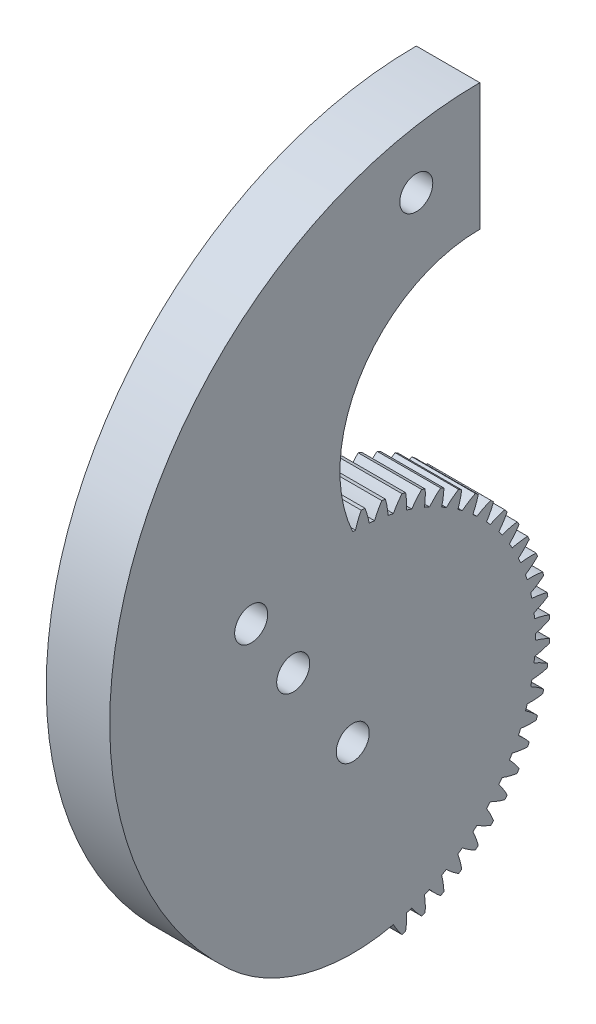
SolidWorks part; units mm, degrees
material "PLA"
ref_plane "Plane1" through (0, 0, 0) normal (0, 0, 1) x (1, 0, 0)
ref_plane "Plane2" through (0, 0, 0) normal (0, 1, 0) x (1, 0, 0)
ref_plane "Plane3" through (0, 0, 0) normal (1, 0, 0) x (0, 0, -1)
sketch "HoldingSke" plane through (0, 0, 0) normal (0, 1, 0) x (1, 0, 0)
  line L0 (0, 0) -> (0.866, -0.5)
  line L1 (-15, 0) -> (100, 0) construction
  line L2 (0, 0) -> (-2.1039, 2.3779)
  line L3 (0, 0) -> (-11.863, 4.5341)
  line L4 (0, 0) -> (7.479, 4.318)
  line L5 (0, 0) -> (-46.8476, -17.4728)
  line L6 (0, 0) -> (-4.9738, -3.3558)
  line L7 (-2.1039, 2.3779) -> (8.6586, 51.2059)
  line L8 (-76.2, 54.61) -> (-75.3, 54.61)
  line L9 (-71.009, 38.7566) -> (-53.1078, 45.2721)
  line L10 (-76.2, 71.12) -> (104.1128, 71.12)
  line L11 (0, 0) -> (-6, 0)
  line L12 (-76.2, 101.6) -> (-76.162, 101.6)
  line L13 (24.9733, 27.94) -> (52.9518, 28.4284)
  line L14 (24.9733, 27.94) -> (24.9743, 27.94)
  line L15 (24.9733, 27.94) -> (100.4006, 29.5858)
  line L16 (-63.627, -1) -> (-12.827, -1)
  circle A0 centre (0, 0) radius 2.5
  circle A1 centre (0, 0) radius 13.749
  circle A2 centre (0, 0) radius 37.5
  circle A3 centre (0, 0) radius 2.5
  dimension "Num_teeth" = 30
  dimension "Pitch_radius" = 180.3128
  dimension "Width" = 6
sketch "BasProSke" plane through (0, 0, 0) normal (0, 1, 0) x (1, 0, 0)
  line L0 (-10, 0) -> (60, 0) construction
  line L1 (0, 0) -> (0, 15.5255)
  line L2 (0, 0) -> (5, 0)
  line L3 (5, 0) -> (5, 15.5255)
  line L4 (5, 15.5255) -> (0, 15.5255)
  dimension "Thickness" = 5
  dimension "Diameter" = 31.051
revolve "Base-Revolve" add sketch "BasProSke" angle 360 about L0
sketch "TooCutSke" plane through (0, 0, 0) normal (1, 0, 0) x (0, 0, -1)
  line L1 (0, 0) -> (0, 107) construction
  line L2 (0, 0) -> (-0.4263, 14.9939) construction
  line L3 (0, 0) -> (-1.5696, 29.9503) construction
  line L4 (-0.4263, 14.9939) -> (-0.7848, 14.9752) construction
  arc A0 (0.2153, 14.3724) -> (-0.2153, 14.3724) centre (0, 0) ccw
  arc A1 (0.6632, 15.5113) -> (-0.6632, 15.5113) centre (0, 0) ccw
  circle A2 centre (0, 0) radius 15 construction
  circle A3 centre (0, 0) radius 14.0954 construction
  arc A4 (-0.2153, 14.3724) -> (-0.6632, 15.5113) centre (-5.9939, 12.7575) ccw
  arc A5 (0.6632, 15.5113) -> (0.2153, 14.3724) centre (5.9939, 12.7575) ccw
extrude "ToothCut" cut sketch "TooCutSke" along normal through all
fillet "Breaks" [suppressed] radius 0.02 tangent propagation no
fillet "RootFillets" [suppressed] radius 0.251
pattern_circular "TeethCuts" count 60 every 6 about axis through (-10, 0, 0) along (1, 0, 0) of "ToothCut"
sketch "HubNeaOneSke" plane through (0, 0, 0) normal (-1, 0, 0) x (0, 0, 1)
  circle A0 centre (0, 0) radius 13.749
  dimension "Diameter" = 27.498
extrude "HubNearOne" [suppressed] add sketch "HubNeaOneSke" along normal blind 45.0001
sketch "HubNeaBotSke" plane through (0, 0, 0) normal (-1, 0, 0) x (0, 0, 1)
  circle A0 centre (0, 0) radius 13.749
  dimension "Diameter" = 27.498
extrude "HubNearBoth" [suppressed] add sketch "HubNeaBotSke" along normal blind 22.5
ref_plane "FarPln" through (5, 0, 0) normal (1, 0, 0) x (0, 0, -1)
sketch "HubFarSke" plane through (5, 0, 0) normal (1, 0, 0) x (0, 0, -1)
  circle A0 centre (0, 0) radius 13.749
  dimension "Diameter" = 27.498
extrude "HubFar" [suppressed] add sketch "HubFarSke" along normal blind 22.5
sketch "BorSke" plane through (0, 0, 0) normal (1, 0, 0) x (0, 0, -1)
  circle A0 centre (0, 0) radius 1.3
  dimension "Diameter" = 2.6
extrude "Bore" cut sketch "BorSke" along normal mid plane 100.0001
sketch "KeySke" plane through (0, 0, 0) normal (1, 0, 0) x (0, 0, -1)
  line L0 (-1, 0) -> (-1, 3.4)
  line L1 (-1, 3.4) -> (1, 3.4)
  line L2 (1, 3.4) -> (1, 0)
  line L3 (0, 0) -> (0, 34) construction
  line L4 (-1, 0) -> (1, 0)
  dimension "Width" = 2
extrude "Keyway" [suppressed] cut sketch "KeySke" along normal mid plane 100.0001
pattern_circular "Keyway2" [suppressed] count 2 every 90 about axis through (-10, 0, 0) along (1, 0, 0) reverse direction yes
sketch "Szkic1" plane through (5, 0, 0) normal (1, 0, 0) x (0, 0, -1)
  line L0 (0, 14.374) -> (0, 20.6333)
  line L1 (2.9482, -14.0684) -> (4.2597, -19.1168)
  arc A0 (-0.731, 20.9085) -> (4.2597, -19.1168) centre (1.7643, 0.8958) ccw
  arc A1 (0, 14.374) -> (2.9482, -14.0684) centre (0, 0) ccw
  arc A2 (2.7776, -14.1031) -> (3.1988, -14.0135) centre (0, 0) ccw construction
  dimension "D1" = 14.374
extrude "Wytnij-wyciągnięcie1" cut sketch "Szkic1" against normal through all and the other way through all contours A0 L1 A1 L0
sketch "Szkic2" plane through (0, 0, 0) normal (1, 0, 0) x (0, 0, -1)
  line L1 (10, 30) -> (10, 40)
  circle A0 centre (0, 0) radius 15.5255 construction
  arc A1 (10, 30) -> (0, 14.374) centre (10, 18.9872) ccw
  arc A2 (0.2153, 14.3724) -> (3.1988, -14.0135) centre (0, 0) ccw construction
  arc A3 (10, 40) -> (-9.7357, -10.5748) centre (10, 10.8619) ccw
  arc A4 (-9.7357, -10.5748) -> (0, 14.374) centre (0, 0) cw
  arc A5 (0.9618, 15.4957) -> (0.6632, 15.5113) centre (0, 0) ccw construction
  dimension "D3" = 10
  dimension "D1" = 40
  dimension "D2" = 10
extrude "Dodanie-wyciągnięcie1" add sketch "Szkic2" along normal up to surface (5 mm away) up to face at (5, 0, 1.3)
hole_wizard "Otwór pod śrubę M21" positions "Szkic3" profile "Szkic4" hole size "M2" standard "ISO" end condition up to next
sketch "Szkic3" plane through (5, 0, 0) normal (1, 0, 0) x (0, 0, -1)
  line L0 (10, 40) -> (10, 30) construction
  point P0 (5, 35)
  dimension "D1" = 5
  dimension "D2" = 5
sketch "Szkic4" plane through (5, 35, -5) normal (0, 1, 0) x (0, 0, -1)
  line L0 (0, 0) -> (0, 5)
  line L1 (0, 5) -> (1.3, 5)
  line L2 (1.3, 5) -> (1.3, 0)
  line L5 (1.3, 0) -> (0, 0)
  line L11 (0, -6.35) -> (0, 107.95) construction
  dimension "Średnica otworu na wylot" = 2.6
  dimension "Głębokość otworu na wylot" = 5
hole_wizard "Otwór pod śrubę M22" positions "Szkic6" profile "Szkic7" hole size "M2" standard "ISO" end condition up to next
sketch "Szkic6" plane through (5, 0, 0) normal (1, 0, 0) x (0, 0, -1)
  line L0 (0, 0) -> (-8, 12.0934) construction
  circle A0 centre (0, 0) radius 1.3 construction
  circle A1 centre (0, 0) radius 1.3 construction
  point P0 (-8, 12.0934)
  point P9 (-4.6897, 7.0892)
  dimension "D1" = 14.5
  dimension "D2" = 8
  dimension "D3" = 6
sketch "Szkic7" plane through (5, 12.0934, 8) normal (0, 1, 0) x (0, 0, -1)
  line L0 (0, 0) -> (0, 5)
  line L1 (0, 5) -> (1.3, 5)
  line L2 (1.3, 5) -> (1.3, 0)
  line L5 (1.3, 0) -> (0, 0)
  line L11 (0, -6.35) -> (0, 107.95) construction
  dimension "Średnica otworu na wylot" = 2.6
  dimension "Głębokość otworu na wylot" = 5
sketch "Szkic8" plane through (0, 0, 0) normal (1, 0, 0) x (0, 0, -1)
  circle A0 centre (0, 0) radius 3.4
  dimension "D1" = 6.8
extrude "Wytnij-wyciągnięcie2" cut sketch "Szkic8" along normal blind 2
ref_plane "Blat stołu" through (5, 0, 0) normal (1, 0, 0) x (0, 0, -1)
equation "' \"Module@HoldingSke\" = 6.35"
equation "' \"Num_teeth@HoldingSke\" = 12"
equation "' \"Ap@HoldingSke\" =  20"
equation "' \"Ap@HoldingSke\" = 20"
equation "' \"Width@HoldingSke\" = 0.5 * 25.4"
equation "' \"Hub_dia@HoldingSke\"= 1 * 25.4"
equation "' \"Hub_dia@HoldingSke\" = 1 * 25.4"
equation "' \"Overall_len@HoldingSke\" = 1.0 * 25.4"
equation "' \"Bore@HoldingSke\" = 0.75 * 25.4"
equation "' \"T_dim@HoldingSke\" = 0.1 * 25.4"
equation "' \"Width@KeySke\" = 0.25 * 25.4"
equation "' \"Show_teeth@HoldingSke\" = 13"
equation "' \"Backlash@HoldingSke\" = 0.009 * 25.4"
equation "' \"Addendum_fac@HoldingSke\" = 1.0"
equation "' \"Dedendum_fac@HoldingSke\" = 1.25"
equation "' \"Dedendum_add@HoldingSke\" = 0.00005 * 25.4"
equation "' \"Clearance_fac@HoldingSke\" = 0.25"
equation "\"Pitch@HoldingSke\" = 1 / \"Module@HoldingSke\""
equation "\"Pitch_dia@TooCutSke\" = \"Num_teeth@HoldingSke\" / \"Pitch@HoldingSke\""
equation "\"Base_dia@TooCutSke\" = \"Num_teeth@HoldingSke\" / \"Pitch@HoldingSke\" * cos((\"Ap@HoldingSke\"  * 3.14159265 / 180))"
equation "\"Flank_rad@TooCutSke\" = \"Num_teeth@HoldingSke\" / \"Pitch@HoldingSke\" / 5"
equation "\"Radius@RootFillets\" = \"Clearance_fac@HoldingSke\" / \"Pitch@HoldingSke\" + \"Dedendum_add@HoldingSke\""
equation "\"Break_rad@Breaks\" = 0.02 / \"Pitch@HoldingSke\""
equation "\"Thickness@HoldingSke\" = \"Width@HoldingSke\""
equation "\"OAL@HoldingSke\" = \"Thickness@HoldingSke\""
equation "\"MHD@HoldingSke\" = (\"Num_teeth@HoldingSke\" + 2) / \"Pitch@HoldingSke\" - 2 * (\"Addendum_fac@HoldingSke\" + \"Dedendum_fac@HoldingSke\")  / \"Pitch@HoldingSke\" - \"Dedendum_add@HoldingSke\" * 2"
equation "\"MBD@HoldingSke\" = (\"Num_teeth@HoldingSke\" + 2) / \"Pitch@HoldingSke\" - 2 * (\"Addendum_fac@HoldingSke\" + \"Dedendum_fac@HoldingSke\")  / \"Pitch@HoldingSke\" - \"Dedendum_add@HoldingSke\" * 2 - 0.002 * 25.4"
equation "\"MHD@HoldingSke\" = ((sgn( \"MHD@HoldingSke\" - \"Hub_dia@HoldingSke\" )-1)*( \"MHD@HoldingSke\" - \"Hub_dia@HoldingSke\" ))/-2+ \"Hub_dia@HoldingSke\""
equation "\"MBD@HoldingSke\" = ((sgn( \"MBD@HoldingSke\" - \"Bore@HoldingSke\" )-1)*( \"MBD@HoldingSke\" - \"Bore@HoldingSke\" ))/-2+ \"Bore@HoldingSke\""
equation "\"OAL@HoldingSke\" = ((sgn( \"OAL@HoldingSke\" - \"Overall_len@HoldingSke\" )+1)*( \"OAL@HoldingSke\" - \"Overall_len@HoldingSke\" ))/2 + \"Overall_len@HoldingSke\" + 0.000002 * 25.4"
equation "\"Num_teeth@TeethCuts\" = ((sgn( \"Num_teeth@TeethCuts\" - 2.0)+1)*( \"Num_teeth@TeethCuts\" - 2.0))/2 +2.0"
equation "' \"Fillet_rad@BasProSke\" =  \"Thickness@HoldingSke\" * 0.05"
equation "' \"Fillet_rad@BasProSke\" = \"Thickness@HoldingSke\" * 0.05"
equation "\"MHD@HoldingSke\" = ((sgn( \"MHD@HoldingSke\" - \"Root_dia@TooCutSke\" )-1)*( \"MHD@HoldingSke\" - \"Root_dia@TooCutSke\" ))/-2+ \"Root_dia@TooCutSke\""
equation "\"Diameter@HubNeaOneSke\" = \"MHD@HoldingSke\""
equation "\"Length@HubNearOne\" = \"OAL@HoldingSke\" - \"Thickness@BasProSke\""
equation "\"Diameter@HubNeaBotSke\" = \"MHD@HoldingSke\""
equation "\"Length@HubNearBoth\" = ( \"OAL@HoldingSke\" - \"Thickness@BasProSke\" ) / 2.0"
equation "\"Thickness@FarPln\" = \"Thickness@BasProSke\""
equation "\"Diameter@HubFarSke\" = \"MHD@HoldingSke\""
equation "\"Length@HubFar\" = ( \"OAL@HoldingSke\" - \"Thickness@BasProSke\" ) / 2.0"
equation "\"D1@Bore\" = \"OAL@HoldingSke\" * 2.0"
equation "\"D1@Keyway\" = \"OAL@HoldingSke\" * 2.0"
equation "\"Offset@KeySke\" = \"T_dim@HoldingSke\" + \"MBD@HoldingSke\" / 2.0"
